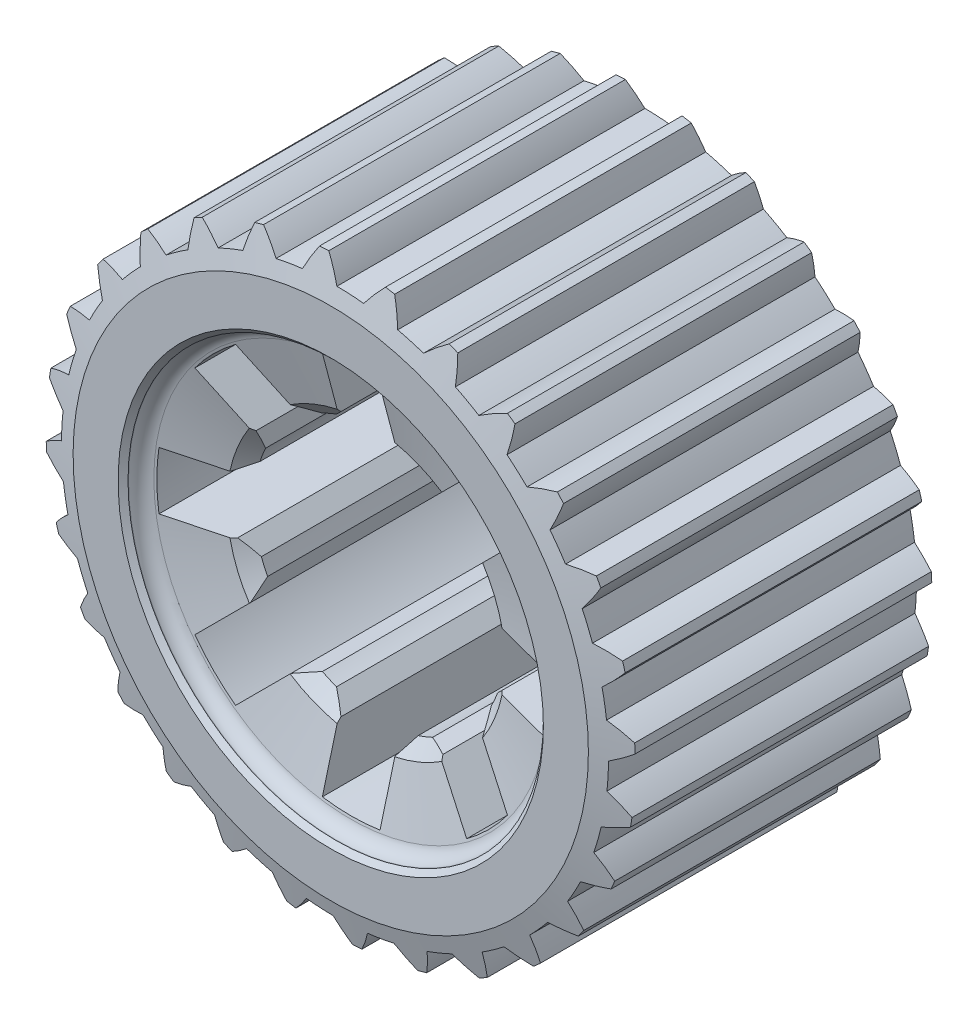
SolidWorks part; units mm, degrees
material "PB01 (C90710) Bronze"
ref_plane "Front" through (0, 0, 0) normal (0, 0, 1) x (1, 0, 0)
ref_plane "Top" through (0, 0, 0) normal (0, 1, 0) x (1, 0, 0)
ref_plane "Right" through (0, 0, 0) normal (1, 0, 0) x (0, 0, -1)
sketch "Sketch1" plane through (0, 0, 0) normal (1, 0, 0) x (0, 0, -1)
  line L0 (0, 0) -> (32, 0) construction
  line L1 (1.0048, 29.8) -> (30.9952, 29.8)
  line L2 (0, 21.5) -> (0, 26.05)
  line L3 (32, 26.05) -> (32, 21.5)
  line L4 (4.9261, 12.7) -> (27.049, 12.7)
  line L5 (0.5, 21) -> (0.5511, 21)
  line L6 (0, 21.5) -> (0.5, 21)
  line L7 (32, 21.5) -> (31.5, 21)
  line L8 (31.4489, 21) -> (31.5, 21)
  line L9 (0, 26.05) -> (1.0048, 29.8)
  line L10 (0, 12.7) -> (32, 12.7) construction
  line L11 (2, 19.8882) -> (3.5601, 14.066)
  line L12 (0, 21) -> (32, 21) construction
  line L13 (32, 26.05) -> (30.9952, 29.8)
  line L14 (3.5601, 14.066) -> (4.9261, 12.7)
  line L15 (0, 29.8) -> (32, 29.8) construction
  line L16 (30, 19.8882) -> (28.449, 14.1)
  line L17 (28.449, 14.1) -> (27.049, 12.7)
  arc A0 (31.4489, 21) -> (30, 19.8882) centre (31.4489, 19.5) ccw
  arc A1 (2, 19.8882) -> (0.5511, 21) centre (0.5511, 19.5) ccw
  point P9 (2, 0)
  point P10 (2, 29.8)
  point P11 (30, 29.8)
  point P12 (30, 0)
  point P14 (28.0739, 12.7)
  point P17 (3.9261, 12.7)
  point P19 (30.2979, 21)
  point P22 (1.7021, 21)
  dimension "D9" = 1.5
  dimension "D1" = 32
  dimension "D2" = 15
  dimension "D3" = 15
  dimension "D4" = 2
  dimension "D5" = 2
  dimension "D6" = 21
  dimension "D7" = 29.8
  dimension "D8" = 12.7
  dimension "D11" = 45
  dimension "D13" = 45
  dimension "D14" = 15
  dimension "D15" = 15
  dimension "D16" = 26.05
  dimension "D17" = 26.05
  dimension "D18" = 1
  dimension "D19" = 45
  dimension "D20" = 1.366
  dimension "D21" = 1.366
  dimension "D22" = 1.4
  dimension "D23" = 45
  dimension "D24" = 1.4
revolve "Revolve1" add sketch "Sketch1" angle 360 about L0
sketch "Sketch2" plane through (0, 0, 0) normal (0, 0, 1) x (1, 0, 0)
  line L0 (2.915, 12.3609) -> (2.915, 19.4326)
  line L1 (19.65, 0) -> (0, 0) construction
  line L2 (2.915, -19.65) -> (2.915, -19.4326)
  line L3 (-2.915, -19.65) -> (-2.915, -19.4326)
  line L4 (6.6793, 10.8017) -> (11.6797, 15.8021)
  line L5 (10.8017, 6.6793) -> (15.8021, 11.6797)
  line L6 (-2.915, 12.3609) -> (-2.915, 19.4326)
  line L7 (12.3609, 2.915) -> (19.4326, 2.915)
  line L8 (-2.915, 0) -> (-2.915, 19.65) construction
  line L9 (0, 0) -> (0, 19.65) construction
  line L10 (2.915, 0) -> (2.915, 19.65) construction
  line L11 (12.3609, -2.915) -> (19.4326, -2.915)
  line L12 (10.8017, -6.6793) -> (15.8021, -11.6797)
  line L13 (6.6793, -10.8017) -> (11.6797, -15.8021)
  line L14 (2.915, -12.3609) -> (2.915, -19.4326)
  line L15 (-2.915, -12.3609) -> (-2.915, -19.4326)
  line L16 (-6.6793, -10.8017) -> (-11.6797, -15.8021)
  line L17 (-10.8017, -6.6793) -> (-15.8021, -11.6797)
  line L18 (-12.3609, -2.915) -> (-19.4326, -2.915)
  line L19 (-12.3609, 2.915) -> (-19.4326, 2.915)
  line L20 (-10.8017, 6.6793) -> (-15.8021, 11.6797)
  line L21 (-6.6793, 10.8017) -> (-11.6797, 15.8021)
  circle A0 centre (0, 0) radius 12.7 construction
  arc A1 (-6.6793, 10.8017) -> (-10.8017, 6.6793) centre (0, 0) ccw
  arc A2 (-11.6797, 15.8021) -> (-15.8021, 11.6797) centre (0, 0) ccw
  arc A3 (2.915, 12.3609) -> (-2.915, 12.3609) centre (0, 0) ccw
  arc A4 (2.915, 19.4326) -> (-2.915, 19.4326) centre (0, 0) ccw
  arc A5 (15.8021, 11.6797) -> (11.6797, 15.8021) centre (0, 0) ccw
  arc A6 (10.8017, 6.6793) -> (6.6793, 10.8017) centre (0, 0) ccw
  arc A7 (19.4326, -2.915) -> (19.4326, 2.915) centre (0, 0) ccw
  arc A8 (12.3609, -2.915) -> (12.3609, 2.915) centre (0, 0) ccw
  arc A9 (11.6797, -15.8021) -> (15.8021, -11.6797) centre (0, 0) ccw
  arc A10 (6.6793, -10.8017) -> (10.8017, -6.6793) centre (0, 0) ccw
  arc A11 (-2.915, -19.4326) -> (2.915, -19.4326) centre (0, 0) ccw
  arc A12 (-2.915, -12.3609) -> (2.915, -12.3609) centre (0, 0) ccw
  arc A13 (-10.8017, -6.6793) -> (-6.6793, -10.8017) centre (0, 0) ccw
  arc A14 (-15.8021, -11.6797) -> (-11.6797, -15.8021) centre (0, 0) ccw
  arc A15 (-19.4326, 2.915) -> (-19.4326, -2.915) centre (0, 0) ccw
  arc A16 (-12.3609, 2.915) -> (-12.3609, -2.915) centre (0, 0) ccw
  point P4 (0, -19.65)
  point P50 (0, 0)
  dimension "D1" = 39.3
  dimension "D2" = 2.915
  dimension "D3" = 5.83
  dimension "D4" = 8
extrude "Cut-Extrude1" cut sketch "Sketch2" against normal up to surface (32 mm away) contours A16 L19 A15 L18 | L21 A2 L20 A1 | L0 A4 L6 A3 | A6 L5 A5 L4 | A8 L11 A7 L7 | A10 L13 A9 L12 | A12 L15 A11 L14 | L17 A14 L16 A13 up to face at (26.05, 0, -32)
sketch "Sketch4" plane through (0, 0, 0) normal (0, 0, 1) x (1, 0, 0)
  line L0 (0, 0) -> (0, 28) construction
  line L1 (-18.7611, 28) -> (23.3433, 28) construction
  line L2 (0, 28) -> (22.339, 40.8974) construction
  line L3 (0, 28) -> (-36.8433, 6.7285) construction
  line L4 (0, 0) -> (-12.1244, 21) construction
  line L5 (0, 0) -> (-9.6241, 22.257) construction
  line L6 (0, 0) -> (-6.9957, 23.2177) construction
  line L7 (0, 0) -> (-4.2741, 23.8691) construction
  line L8 (0, 0) -> (-1.4956, 24.2025) construction
  line L9 (0, 0) -> (1.3028, 24.2137) construction
  line L10 (-9.6241, 22.257) -> (0.656, 26.7022) construction
  line L11 (-6.9957, 23.2177) -> (1.0471, 25.6411) construction
  line L12 (-4.2741, 23.8691) -> (1.2382, 24.8561) construction
  line L13 (-1.4956, 24.2025) -> (1.299, 24.3752) construction
  circle A0 centre (0, 0) radius 28
  circle A1 centre (0, 0) radius 24.2487
  point P10 (-9.6995, 22.4)
  point P16 (-7.2746, 23.8)
  point P17 (-4.8497, 25.2)
  point P18 (-2.4249, 26.6)
  dimension "D1" = 56
  dimension "D2" = 30
  dimension "D3" = 14
  dimension "D4" = 2.8
  dimension "D5" = 2.8
  dimension "D6" = 2.8
  dimension "D7" = 2.8
  dimension "D8" = 2.8
  dimension "D14" = 11.2
  dimension "D15" = 8.4
  dimension "D16" = 5.6
  dimension "D17" = 11.2
  dimension "D18" = 8.4
  dimension "D19" = 5.6
  dimension "D20" = 2.8
  dimension "D9" = 2.8
  dimension "D10" = 2.8
  dimension "D11" = 2.8
  dimension "D12" = 2.8
  dimension "D13" = 2.8
sketch "Sketch5" plane through (0, 0, 0) normal (0, 0, 1) x (1, 0, 0)
  line L0 (0, 0) -> (-14.4631, 19.4633) construction
  line L1 (0, 0) -> (-16.6092, 17.6673) construction
  line L2 (0, 0) -> (-18.5341, 15.636) construction
  line L3 (0, 0) -> (-20.2122, 13.3965) construction
  line L4 (0, 0) -> (-21.6211, 10.9786) construction
  line L5 (0, 28) -> (-36.8433, 6.7285) construction
  line L6 (-14.4631, 19.4633) -> (-0.9786, 29.4836) construction
  line L7 (-16.6092, 17.6673) -> (-2.3289, 31.0924) construction
  line L8 (-18.5341, 15.636) -> (-4.0902, 32.7571) construction
  line L9 (-20.2122, 13.3965) -> (-6.2901, 34.4017) construction
  line L10 (-21.6211, 10.9786) -> (-8.9441, 35.9445) construction
  circle A0 centre (0, 0) radius 24.2487 construction
  circle A1 centre (0, 0) radius 28 construction
  point P9 (-24.2487, 14)
  point P10 (-21.8238, 15.4)
  point P15 (-19.399, 16.8)
  point P16 (-16.9741, 18.2)
  point P17 (-14.5492, 19.6)
  dimension "D4" = 2.8
  dimension "D5" = 2.8
  dimension "D6" = 2.8
  dimension "D7" = 2.8
  dimension "D8" = 2.8
  dimension "D9" = 2.8
  dimension "D10" = 2.8
  dimension "D11" = 2.8
  dimension "D1" = 14
  dimension "D2" = 2.8
  dimension "D3" = 2.8
  dimension "D12" = 16.8
  dimension "D13" = 19.6
  dimension "D14" = 22.4
  dimension "D15" = 25.2
  dimension "D16" = 28
  dimension "D17" = 28
  dimension "D18" = 25.2
  dimension "D19" = 22.4
  dimension "D20" = 19.6
  dimension "D21" = 16.8
sketch "Sketch6" plane through (0, 0, 0) normal (0, 0, 1) x (1, 0, 0)
  line L0 (0, 0) -> (-1.5692, 27.956) construction
  circle A0 centre (0, 0) radius 30
  circle A1 centre (0, 0) radius 27.65
  circle A2 centre (0, 0) radius 28 construction
  spline S0 degree 3 poles (1.3028, 24.2137) (1.3049, 24.4294) (1.2419, 24.912) (1.0334, 25.7495) (0.6351, 26.8109) (-0.0275, 28.1087) (-1.0134, 29.5922) (-2.3714, 31.2006) (-4.888, 33.5671) (-7.2163, 35.0662) (-8.9441, 35.9445) knots 0 0 0 0 0.040002 0.090002 0.160002 0.250002 0.360002 0.490002 0.640001 1 1 1 1
  spline S1 degree 3 poles (-4.0043, 23.9158) (-4.0305, 24.1299) (-4.0219, 24.6166) (-3.9085, 25.4721) (-3.6314, 26.5714) (-3.1183, 27.9353) (-2.447, 29.2425) (-1.9239, 30.0741) (-1.7062, 30.3969) knots 0 0 0 0 0.040002 0.090002 0.160002 0.250002 0.360002 0.432252 0.432252 0.432252 0.432252
  dimension "D1" = 60
  dimension "D2" = 55.3
  dimension "D3" = 1.57
sketch "Sketch7" plane through (0, 0, 0) normal (0, 0, 1) x (1, 0, 0)
  circle A0 centre (0, 0) radius 30 construction
  circle A1 centre (0, 0) radius 27.65 construction
  arc A2 (-2.009, 29.9327) -> (-7.9882, 28.9169) centre (0, 0) ccw
  arc A3 (-3.2887, 27.4537) -> (-5.9617, 26.9996) centre (0, 0) ccw
  arc A4 (2.9028, 27.4972) -> (0.1957, 27.6493) centre (0, 0) ccw
  arc A5 (4.702, 29.6292) -> (-1.3533, 29.9695) centre (0, 0) ccw
  arc A6 (8.9487, 26.1619) -> (6.3434, 26.9125) centre (0, 0) ccw
  arc A7 (11.1772, 27.8401) -> (5.3495, 29.5192) centre (0, 0) ccw
  arc A8 (14.5459, 23.5146) -> (12.1729, 24.8262) centre (0, 0) ccw
  arc A9 (17.092, 24.6549) -> (11.784, 27.5887) centre (0, 0) ccw
  arc A10 (19.4137, 19.6883) -> (17.3921, 21.4951) centre (0, 0) ccw
  arc A11 (22.1497, 20.2334) -> (17.6276, 24.2748) centre (0, 0) ccw
  arc A12 (23.3081, 14.8747) -> (21.7391, 17.086) centre (0, 0) ccw
  arc A13 (26.0967, 14.7974) -> (22.5873, 19.7437) centre (0, 0) ccw
  arc A14 (26.0336, 9.3152) -> (24.9961, 11.8203) centre (0, 0) ccw
  arc A15 (28.7351, 8.6193) -> (26.4144, 14.2225) centre (0, 0) ccw
  arc A16 (27.4537, 3.2887) -> (26.9996, 5.9617) centre (0, 0) ccw
  arc A17 (29.9327, 2.009) -> (28.9169, 7.9882) centre (0, 0) ccw
  arc A18 (27.4972, -2.9028) -> (27.6493, -0.1957) centre (0, 0) ccw
  arc A19 (29.6292, -4.702) -> (29.9695, 1.3533) centre (0, 0) ccw
  arc A20 (26.1619, -8.9487) -> (26.9125, -6.3434) centre (0, 0) ccw
  arc A21 (27.8401, -11.1772) -> (29.5192, -5.3495) centre (0, 0) ccw
  arc A22 (23.5146, -14.5459) -> (24.8262, -12.1729) centre (0, 0) ccw
  arc A23 (24.6549, -17.092) -> (27.5887, -11.784) centre (0, 0) ccw
  arc A24 (19.6883, -19.4137) -> (21.4951, -17.3921) centre (0, 0) ccw
  arc A25 (20.2334, -22.1497) -> (24.2748, -17.6276) centre (0, 0) ccw
  arc A26 (14.7974, -26.0967) -> (19.7437, -22.5873) centre (0, 0) ccw
  arc A27 (14.8747, -23.3081) -> (17.086, -21.7391) centre (0, 0) ccw
  arc A28 (9.3152, -26.0336) -> (11.8203, -24.9961) centre (0, 0) ccw
  arc A29 (8.6193, -28.7351) -> (14.2225, -26.4144) centre (0, 0) ccw
  arc A30 (3.2887, -27.4537) -> (5.9617, -26.9996) centre (0, 0) ccw
  arc A31 (2.009, -29.9327) -> (7.9882, -28.9169) centre (0, 0) ccw
  arc A32 (-2.9028, -27.4972) -> (-0.1957, -27.6493) centre (0, 0) ccw
  arc A33 (-4.702, -29.6292) -> (1.3533, -29.9695) centre (0, 0) ccw
  arc A34 (-8.9487, -26.1619) -> (-6.3434, -26.9125) centre (0, 0) ccw
  arc A35 (-11.1772, -27.8401) -> (-5.3495, -29.5192) centre (0, 0) ccw
  arc A36 (-14.5459, -23.5146) -> (-12.1729, -24.8262) centre (0, 0) ccw
  arc A37 (-17.092, -24.6549) -> (-11.784, -27.5887) centre (0, 0) ccw
  arc A38 (-19.4137, -19.6883) -> (-17.3921, -21.4951) centre (0, 0) ccw
  arc A39 (-22.1497, -20.2334) -> (-17.6276, -24.2748) centre (0, 0) ccw
  arc A40 (-23.3081, -14.8747) -> (-21.7391, -17.086) centre (0, 0) ccw
  arc A41 (-26.0967, -14.7974) -> (-22.5873, -19.7437) centre (0, 0) ccw
  arc A42 (-26.0336, -9.3152) -> (-24.9961, -11.8203) centre (0, 0) ccw
  arc A43 (-28.7351, -8.6193) -> (-26.4144, -14.2225) centre (0, 0) ccw
  arc A44 (-27.4537, -3.2887) -> (-26.9996, -5.9617) centre (0, 0) ccw
  arc A45 (-29.9327, -2.009) -> (-28.9169, -7.9882) centre (0, 0) ccw
  arc A46 (-27.4972, 2.9028) -> (-27.6493, 0.1957) centre (0, 0) ccw
  arc A47 (-29.6292, 4.702) -> (-29.9695, -1.3533) centre (0, 0) ccw
  arc A48 (-26.1619, 8.9487) -> (-26.9125, 6.3434) centre (0, 0) ccw
  arc A49 (-27.8401, 11.1772) -> (-29.5192, 5.3495) centre (0, 0) ccw
  arc A50 (-23.5146, 14.5459) -> (-24.8262, 12.1729) centre (0, 0) ccw
  arc A51 (-24.6549, 17.092) -> (-27.5887, 11.784) centre (0, 0) ccw
  arc A52 (-19.6883, 19.4137) -> (-21.4951, 17.3921) centre (0, 0) ccw
  arc A53 (-20.2334, 22.1497) -> (-24.2748, 17.6276) centre (0, 0) ccw
  arc A54 (-14.8747, 23.3081) -> (-17.086, 21.7391) centre (0, 0) ccw
  arc A55 (-14.7974, 26.0967) -> (-19.7437, 22.5873) centre (0, 0) ccw
  arc A56 (-9.3152, 26.0336) -> (-11.8203, 24.9961) centre (0, 0) ccw
  arc A57 (-8.6193, 28.7351) -> (-14.2225, 26.4144) centre (0, 0) ccw
  spline S0 degree 3 poles (-1997.3661, 89.5361) (-18.209, 0.2675) (3.6062, 15.4141) (1.0334, 25.7495) (0.6351, 26.8109) (-0.0275, 28.1087) (-1.0134, 29.5922) (-2.3714, 31.2006) (-49.6157, 75.6264) (-271.632, -90.4138) (1988.1458, -19.2595) knots -1.814677 -1.814677 -1.814677 -1.814677 0.040002 0.090002 0.160002 0.250002 0.360002 0.490002 0.640001 12.374487 12.374487 12.374487 12.374487 only from (1.3028, 24.2137) to (-8.9441, 35.9445) construction
  spline S1 degree 3 poles (1974.8351, 312.5004) (18.0649, 2.3034) (-5.3085, 14.9136) (-3.9085, 25.4721) (-3.6314, 26.5714) (-3.1183, 27.9353) (19.7348, 72.4352) (229.3624, 6.3917) (-1971.1728, -314.9823) knots -1.814688 -1.814688 -1.814688 -1.814688 0.040002 0.090002 0.160002 0.250002 0.360002 9.427879 9.427879 9.427879 9.427879 only from (-4.0043, 23.9158) to (-1.7062, 30.3969) construction
  spline S2 degree 3 poles (0.1957, 27.6493) (0.1322, 27.7672) (-0.2221, 28.4016) (-0.7384, 29.1785) (-1.2255, 29.8097) (-1.3533, 29.9695) knots 0.225159 0.225159 0.225159 0.225159 0.250002 0.360002 0.397961 0.397961 0.397961 0.397961
  spline S3 degree 3 poles (-3.2887, 27.4537) (-3.2387, 27.578) (-2.9576, 28.2481) (-2.5315, 29.0778) (-2.1181, 29.7596) (-2.009, 29.9327) knots 0.225159 0.225159 0.225159 0.225159 0.250002 0.360002 0.397961 0.397961 0.397961 0.397961
  spline S4 degree 3 poles (2.9028, 27.4972) (2.9791, 27.6072) (3.4023, 28.198) (4.0024, 28.9121) (4.5571, 29.4848) (4.702, 29.6292) knots 0.225159 0.225159 0.225159 0.225159 0.250002 0.360002 0.397961 0.397961 0.397961 0.397961
  spline S5 degree 3 poles (6.3434, 26.9125) (6.3077, 27.0416) (6.1034, 27.739) (5.7729, 28.6112) (5.4385, 29.335) (5.3495, 29.5192) knots 0.225159 0.225159 0.225159 0.225159 0.250002 0.360002 0.397961 0.397961 0.397961 0.397961
  spline S6 degree 3 poles (8.9487, 26.1619) (9.0476, 26.2521) (9.5916, 26.7339) (10.3356, 27.2966) (11.0039, 27.7315) (11.1772, 27.8401) knots 0.225159 0.225159 0.225159 0.225159 0.250002 0.360002 0.397961 0.397961 0.397961 0.397961
  spline S7 degree 3 poles (12.1729, 24.8262) (12.1668, 24.96) (12.1229, 25.6854) (11.9948, 26.6093) (11.8298, 27.3894) (11.784, 27.5887) knots 0.225159 0.225159 0.225159 0.225159 0.250002 0.360002 0.397961 0.397961 0.397961 0.397961
  spline S8 degree 3 poles (14.5459, 23.5146) (14.6624, 23.5806) (15.3, 23.9293) (16.1505, 24.3123) (16.8988, 24.5876) (17.092, 24.6549) knots 0.225159 0.225159 0.225159 0.225159 0.250002 0.360002 0.397961 0.397961 0.397961 0.397961
  spline S9 degree 3 poles (17.3921, 21.4951) (17.4159, 21.6268) (17.5345, 22.3438) (17.6152, 23.273) (17.6279, 24.0703) (17.6276, 24.2748) knots 0.225159 0.225159 0.225159 0.225159 0.250002 0.360002 0.397961 0.397961 0.397961 0.397961
  spline S10 degree 3 poles (19.4137, 19.6883) (19.542, 19.7267) (20.2412, 19.9248) (21.1556, 20.109) (21.9464, 20.2108) (22.1497, 20.2334) knots 0.225159 0.225159 0.225159 0.225159 0.250002 0.360002 0.397961 0.397961 0.397961 0.397961
  spline S11 degree 3 poles (21.7391, 17.086) (21.7917, 17.2092) (22.0668, 17.8818) (22.3523, 18.7698) (22.5421, 19.5442) (22.5873, 19.7437) knots 0.225159 0.225159 0.225159 0.225159 0.250002 0.360002 0.397961 0.397961 0.397961 0.397961
  spline S12 degree 3 poles (23.3081, 14.8747) (23.4416, 14.8836) (24.1674, 14.9211) (25.0998, 14.8972) (25.8935, 14.8206) (26.0967, 14.7974) knots 0.225159 0.225159 0.225159 0.225159 0.250002 0.360002 0.397961 0.397961 0.397961 0.397961
  spline S13 degree 3 poles (24.9961, 11.8203) (25.0747, 11.9286) (25.4926, 12.5231) (25.9685, 13.3253) (26.3259, 14.0381) (26.4144, 14.2225) knots 0.225159 0.225159 0.225159 0.225159 0.250002 0.360002 0.397961 0.397961 0.397961 0.397961
  spline S14 degree 3 poles (26.0336, 9.3152) (26.1658, 9.2942) (26.8817, 9.1693) (27.7855, 8.9385) (28.5422, 8.6871) (28.7351, 8.6193) knots 0.225159 0.225159 0.225159 0.225159 0.250002 0.360002 0.397961 0.397961 0.397961 0.397961
  spline S15 degree 3 poles (26.9996, 5.9617) (27.1004, 6.0499) (27.6401, 6.5365) (28.2826, 7.2127) (28.7896, 7.8281) (28.9169, 7.9882) knots 0.225159 0.225159 0.225159 0.225159 0.250002 0.360002 0.397961 0.397961 0.397961 0.397961
  spline S16 degree 3 poles (27.4537, 3.2887) (27.578, 3.2387) (28.2481, 2.9576) (29.0778, 2.5315) (29.7596, 2.1181) (29.9327, 2.009) knots 0.225159 0.225159 0.225159 0.225159 0.250002 0.360002 0.397961 0.397961 0.397961 0.397961
  spline S17 degree 3 poles (27.6493, -0.1957) (27.7672, -0.1322) (28.4016, 0.2221) (29.1785, 0.7384) (29.8097, 1.2255) (29.9695, 1.3533) knots 0.225159 0.225159 0.225159 0.225159 0.250002 0.360002 0.397961 0.397961 0.397961 0.397961
  spline S18 degree 3 poles (27.4972, -2.9028) (27.6072, -2.9791) (28.198, -3.4023) (28.9121, -4.0024) (29.4848, -4.5571) (29.6292, -4.702) knots 0.225159 0.225159 0.225159 0.225159 0.250002 0.360002 0.397961 0.397961 0.397961 0.397961
  spline S19 degree 3 poles (26.9125, -6.3434) (27.0416, -6.3077) (27.739, -6.1034) (28.6112, -5.7729) (29.335, -5.4385) (29.5192, -5.3495) knots 0.225159 0.225159 0.225159 0.225159 0.250002 0.360002 0.397961 0.397961 0.397961 0.397961
  spline S20 degree 3 poles (26.1619, -8.9487) (26.2521, -9.0476) (26.7339, -9.5916) (27.2966, -10.3356) (27.7315, -11.0039) (27.8401, -11.1772) knots 0.225159 0.225159 0.225159 0.225159 0.250002 0.360002 0.397961 0.397961 0.397961 0.397961
  spline S21 degree 3 poles (24.8262, -12.1729) (24.96, -12.1668) (25.6854, -12.1229) (26.6093, -11.9948) (27.3894, -11.8298) (27.5887, -11.784) knots 0.225159 0.225159 0.225159 0.225159 0.250002 0.360002 0.397961 0.397961 0.397961 0.397961
  spline S22 degree 3 poles (23.5146, -14.5459) (23.5806, -14.6624) (23.9293, -15.3) (24.3123, -16.1505) (24.5876, -16.8988) (24.6549, -17.092) knots 0.225159 0.225159 0.225159 0.225159 0.250002 0.360002 0.397961 0.397961 0.397961 0.397961
  spline S23 degree 3 poles (21.4951, -17.3921) (21.6268, -17.4159) (22.3438, -17.5345) (23.273, -17.6152) (24.0703, -17.6279) (24.2748, -17.6276) knots 0.225159 0.225159 0.225159 0.225159 0.250002 0.360002 0.397961 0.397961 0.397961 0.397961
  spline S24 degree 3 poles (19.6883, -19.4137) (19.7267, -19.542) (19.9248, -20.2412) (20.109, -21.1556) (20.2108, -21.9464) (20.2334, -22.1497) knots 0.225159 0.225159 0.225159 0.225159 0.250002 0.360002 0.397961 0.397961 0.397961 0.397961
  spline S25 degree 3 poles (17.086, -21.7391) (17.2092, -21.7917) (17.8818, -22.0668) (18.7698, -22.3523) (19.5442, -22.5421) (19.7437, -22.5873) knots 0.225159 0.225159 0.225159 0.225159 0.250002 0.360002 0.397961 0.397961 0.397961 0.397961
  spline S26 degree 3 poles (14.8747, -23.3081) (14.8836, -23.4416) (14.9211, -24.1674) (14.8972, -25.0998) (14.8206, -25.8935) (14.7974, -26.0967) knots 0.225159 0.225159 0.225159 0.225159 0.250002 0.360002 0.397961 0.397961 0.397961 0.397961
  spline S27 degree 3 poles (11.8203, -24.9961) (11.9286, -25.0747) (12.5231, -25.4926) (13.3253, -25.9685) (14.0381, -26.3259) (14.2225, -26.4144) knots 0.225159 0.225159 0.225159 0.225159 0.250002 0.360002 0.397961 0.397961 0.397961 0.397961
  spline S28 degree 3 poles (9.3152, -26.0336) (9.2942, -26.1658) (9.1693, -26.8817) (8.9385, -27.7855) (8.6871, -28.5422) (8.6193, -28.7351) knots 0.225159 0.225159 0.225159 0.225159 0.250002 0.360002 0.397961 0.397961 0.397961 0.397961
  spline S29 degree 3 poles (5.9617, -26.9996) (6.0499, -27.1004) (6.5365, -27.6401) (7.2127, -28.2826) (7.8281, -28.7896) (7.9882, -28.9169) knots 0.225159 0.225159 0.225159 0.225159 0.250002 0.360002 0.397961 0.397961 0.397961 0.397961
  spline S30 degree 3 poles (3.2887, -27.4537) (3.2387, -27.578) (2.9576, -28.2481) (2.5315, -29.0778) (2.1181, -29.7596) (2.009, -29.9327) knots 0.225159 0.225159 0.225159 0.225159 0.250002 0.360002 0.397961 0.397961 0.397961 0.397961
  spline S31 degree 3 poles (-0.1957, -27.6493) (-0.1322, -27.7672) (0.2221, -28.4016) (0.7384, -29.1785) (1.2255, -29.8097) (1.3533, -29.9695) knots 0.225159 0.225159 0.225159 0.225159 0.250002 0.360002 0.397961 0.397961 0.397961 0.397961
  spline S32 degree 3 poles (-2.9028, -27.4972) (-2.9791, -27.6072) (-3.4023, -28.198) (-4.0024, -28.9121) (-4.5571, -29.4848) (-4.702, -29.6292) knots 0.225159 0.225159 0.225159 0.225159 0.250002 0.360002 0.397961 0.397961 0.397961 0.397961
  spline S33 degree 3 poles (-6.3434, -26.9125) (-6.3077, -27.0416) (-6.1034, -27.739) (-5.7729, -28.6112) (-5.4385, -29.335) (-5.3495, -29.5192) knots 0.225159 0.225159 0.225159 0.225159 0.250002 0.360002 0.397961 0.397961 0.397961 0.397961
  spline S34 degree 3 poles (-8.9487, -26.1619) (-9.0476, -26.2521) (-9.5916, -26.7339) (-10.3356, -27.2966) (-11.0039, -27.7315) (-11.1772, -27.8401) knots 0.225159 0.225159 0.225159 0.225159 0.250002 0.360002 0.397961 0.397961 0.397961 0.397961
  spline S35 degree 3 poles (-12.1729, -24.8262) (-12.1668, -24.96) (-12.1229, -25.6854) (-11.9948, -26.6093) (-11.8298, -27.3894) (-11.784, -27.5887) knots 0.225159 0.225159 0.225159 0.225159 0.250002 0.360002 0.397961 0.397961 0.397961 0.397961
  spline S36 degree 3 poles (-14.5459, -23.5146) (-14.6624, -23.5806) (-15.3, -23.9293) (-16.1505, -24.3123) (-16.8988, -24.5876) (-17.092, -24.6549) knots 0.225159 0.225159 0.225159 0.225159 0.250002 0.360002 0.397961 0.397961 0.397961 0.397961
  spline S37 degree 3 poles (-17.3921, -21.4951) (-17.4159, -21.6268) (-17.5345, -22.3438) (-17.6152, -23.273) (-17.6279, -24.0703) (-17.6276, -24.2748) knots 0.225159 0.225159 0.225159 0.225159 0.250002 0.360002 0.397961 0.397961 0.397961 0.397961
  spline S38 degree 3 poles (-19.4137, -19.6883) (-19.542, -19.7267) (-20.2412, -19.9248) (-21.1556, -20.109) (-21.9464, -20.2108) (-22.1497, -20.2334) knots 0.225159 0.225159 0.225159 0.225159 0.250002 0.360002 0.397961 0.397961 0.397961 0.397961
  spline S39 degree 3 poles (-21.7391, -17.086) (-21.7917, -17.2092) (-22.0668, -17.8818) (-22.3523, -18.7698) (-22.5421, -19.5442) (-22.5873, -19.7437) knots 0.225159 0.225159 0.225159 0.225159 0.250002 0.360002 0.397961 0.397961 0.397961 0.397961
  spline S40 degree 3 poles (-23.3081, -14.8747) (-23.4416, -14.8836) (-24.1674, -14.9211) (-25.0998, -14.8972) (-25.8935, -14.8206) (-26.0967, -14.7974) knots 0.225159 0.225159 0.225159 0.225159 0.250002 0.360002 0.397961 0.397961 0.397961 0.397961
  spline S41 degree 3 poles (-24.9961, -11.8203) (-25.0747, -11.9286) (-25.4926, -12.5231) (-25.9685, -13.3253) (-26.3259, -14.0381) (-26.4144, -14.2225) knots 0.225159 0.225159 0.225159 0.225159 0.250002 0.360002 0.397961 0.397961 0.397961 0.397961
  spline S42 degree 3 poles (-26.0336, -9.3152) (-26.1658, -9.2942) (-26.8817, -9.1693) (-27.7855, -8.9385) (-28.5422, -8.6871) (-28.7351, -8.6193) knots 0.225159 0.225159 0.225159 0.225159 0.250002 0.360002 0.397961 0.397961 0.397961 0.397961
  spline S43 degree 3 poles (-26.9996, -5.9617) (-27.1004, -6.0499) (-27.6401, -6.5365) (-28.2826, -7.2127) (-28.7896, -7.8281) (-28.9169, -7.9882) knots 0.225159 0.225159 0.225159 0.225159 0.250002 0.360002 0.397961 0.397961 0.397961 0.397961
  spline S44 degree 3 poles (-27.4537, -3.2887) (-27.578, -3.2387) (-28.2481, -2.9576) (-29.0778, -2.5315) (-29.7596, -2.1181) (-29.9327, -2.009) knots 0.225159 0.225159 0.225159 0.225159 0.250002 0.360002 0.397961 0.397961 0.397961 0.397961
  spline S45 degree 3 poles (-27.6493, 0.1957) (-27.7672, 0.1322) (-28.4016, -0.2221) (-29.1785, -0.7384) (-29.8097, -1.2255) (-29.9695, -1.3533) knots 0.225159 0.225159 0.225159 0.225159 0.250002 0.360002 0.397961 0.397961 0.397961 0.397961
  spline S46 degree 3 poles (-27.4972, 2.9028) (-27.6072, 2.9791) (-28.198, 3.4023) (-28.9121, 4.0024) (-29.4848, 4.5571) (-29.6292, 4.702) knots 0.225159 0.225159 0.225159 0.225159 0.250002 0.360002 0.397961 0.397961 0.397961 0.397961
  spline S47 degree 3 poles (-26.9125, 6.3434) (-27.0416, 6.3077) (-27.739, 6.1034) (-28.6112, 5.7729) (-29.335, 5.4385) (-29.5192, 5.3495) knots 0.225159 0.225159 0.225159 0.225159 0.250002 0.360002 0.397961 0.397961 0.397961 0.397961
  spline S48 degree 3 poles (-26.1619, 8.9487) (-26.2521, 9.0476) (-26.7339, 9.5916) (-27.2966, 10.3356) (-27.7315, 11.0039) (-27.8401, 11.1772) knots 0.225159 0.225159 0.225159 0.225159 0.250002 0.360002 0.397961 0.397961 0.397961 0.397961
  spline S49 degree 3 poles (-24.8262, 12.1729) (-24.96, 12.1668) (-25.6854, 12.1229) (-26.6093, 11.9948) (-27.3894, 11.8298) (-27.5887, 11.784) knots 0.225159 0.225159 0.225159 0.225159 0.250002 0.360002 0.397961 0.397961 0.397961 0.397961
  spline S50 degree 3 poles (-23.5146, 14.5459) (-23.5806, 14.6624) (-23.9293, 15.3) (-24.3123, 16.1505) (-24.5876, 16.8988) (-24.6549, 17.092) knots 0.225159 0.225159 0.225159 0.225159 0.250002 0.360002 0.397961 0.397961 0.397961 0.397961
  spline S51 degree 3 poles (-21.4951, 17.3921) (-21.6268, 17.4159) (-22.3438, 17.5345) (-23.273, 17.6152) (-24.0703, 17.6279) (-24.2748, 17.6276) knots 0.225159 0.225159 0.225159 0.225159 0.250002 0.360002 0.397961 0.397961 0.397961 0.397961
  spline S52 degree 3 poles (-19.6883, 19.4137) (-19.7267, 19.542) (-19.9248, 20.2412) (-20.109, 21.1556) (-20.2108, 21.9464) (-20.2334, 22.1497) knots 0.225159 0.225159 0.225159 0.225159 0.250002 0.360002 0.397961 0.397961 0.397961 0.397961
  spline S53 degree 3 poles (-17.086, 21.7391) (-17.2092, 21.7917) (-17.8818, 22.0668) (-18.7698, 22.3523) (-19.5442, 22.5421) (-19.7437, 22.5873) knots 0.225159 0.225159 0.225159 0.225159 0.250002 0.360002 0.397961 0.397961 0.397961 0.397961
  spline S54 degree 3 poles (-14.8747, 23.3081) (-14.8836, 23.4416) (-14.9211, 24.1674) (-14.8972, 25.0998) (-14.8206, 25.8935) (-14.7974, 26.0967) knots 0.225159 0.225159 0.225159 0.225159 0.250002 0.360002 0.397961 0.397961 0.397961 0.397961
  spline S55 degree 3 poles (-11.8203, 24.9961) (-11.9286, 25.0747) (-12.5231, 25.4926) (-13.3253, 25.9685) (-14.0381, 26.3259) (-14.2225, 26.4144) knots 0.225159 0.225159 0.225159 0.225159 0.250002 0.360002 0.397961 0.397961 0.397961 0.397961
  spline S56 degree 3 poles (-9.3152, 26.0336) (-9.2942, 26.1658) (-9.1693, 26.8817) (-8.9385, 27.7855) (-8.6871, 28.5422) (-8.6193, 28.7351) knots 0.225159 0.225159 0.225159 0.225159 0.250002 0.360002 0.397961 0.397961 0.397961 0.397961
  spline S57 degree 3 poles (-5.9617, 26.9996) (-6.0499, 27.1004) (-6.5365, 27.6401) (-7.2127, 28.2826) (-7.8281, 28.7896) (-7.9882, 28.9169) knots 0.225159 0.225159 0.225159 0.225159 0.250002 0.360002 0.397961 0.397961 0.397961 0.397961
  point P123 (0, 0)
extrude "Cut-Extrude2" cut sketch "Sketch7" against normal up to surface (32 mm away) up to face at (26.05, 0, -32)
chamfer "Chamfer1" distance 1 angle 45 16 edges at (-6.6793, -10.8017, -15.9876) (-2.915, -12.3609, -15.9876) (2.915, -12.3609, -15.9876) (6.6793, -10.8017, -15.9876) (10.8017, -6.6793, -15.9876) (12.3609, -2.915, -15.9876) (12.3609, 2.915, -15.9876) (10.8017, 6.6793, -15.9876) (6.6793, 10.8017, -15.9876) (2.915, 12.3609, -15.9876) (-2.915, 12.3609, -15.9876) (-6.6793, 10.8017, -15.9876) (-10.8017, 6.6793, -15.9876) (-12.3609, 2.915, -15.9876) (-12.3609, -2.915, -15.9876) (-10.8017, -6.6793, -15.9876)
equation "\"z\"= 28'No. of Teeth"
equation "\"m\"= 2'Module"
equation "\"a\"= 30'Pressure Angle"
equation "\"d0\"= \"m\" * \"z\"'Mid Ø"
equation "\"hk\"= \"m\""
equation "\"hf\"= \"m\" * 1.2"
equation "\"da\"= \"d0\" + ( \"m\" * 2 )'Outer Ø"
equation "\"df\"= \"d0\" - ( \"hf\" * 2 ) + 4.1'Root Ø"
equation "\"s\"= ( \"m\" * 3.14 ) / 2"
equation "\"D1@Sketch4\"=\"d0\""
equation "\"D2@Sketch4\"=\"a\""
equation "\"D5@Sketch4\"=\"D4@Sketch4\""
equation "\"D6@Sketch4\"=\"D4@Sketch4\""
equation "\"D7@Sketch4\"=\"D4@Sketch4\""
equation "\"D9@Sketch4\"=\"D4@Sketch4\""
equation "\"D10@Sketch4\"=\"D4@Sketch4\""
equation "\"D11@Sketch4\"=\"D4@Sketch4\""
equation "\"D12@Sketch4\"=\"D4@Sketch4\""
equation "\"D13@Sketch4\"=\"D4@Sketch4\""
equation "\"D17@Sketch4\"=\"D14@Sketch4\""
equation "\"D18@Sketch4\"=\"D15@Sketch4\""
equation "\"D19@Sketch4\"=\"D16@Sketch4\""
equation "\"D20@Sketch4\"=\"D8@Sketch4\""
equation "\"D2@Sketch5\"=2.8"
equation "\"D3@Sketch5\"=\"D2@Sketch5\""
equation "\"D4@Sketch5\"=\"D2@Sketch5\""
equation "\"D5@Sketch5\"=\"D2@Sketch5\""
equation "\"D7@Sketch5\"=\"D2@Sketch5\""
equation "\"D8@Sketch5\"=\"D2@Sketch5\""
equation "\"D9@Sketch5\"=\"D2@Sketch5\""
equation "\"D10@Sketch5\"=\"D2@Sketch5\""
equation "\"D11@Sketch5\"=\"D2@Sketch5\""
equation "\"D17@Sketch5\"=\"D16@Sketch5\""
equation "\"D18@Sketch5\"=\"D15@Sketch5\""
equation "\"D19@Sketch5\"=\"D14@Sketch5\""
equation "\"D20@Sketch5\"=\"D13@Sketch5\""
equation "\"D21@Sketch5\"=\"D12@Sketch5\""
equation "\"D1@Sketch6\"=\"da\""
equation "\"D2@Sketch6\"=\"df\""
equation "\"D3@Sketch6\"=\"s\"/2"
